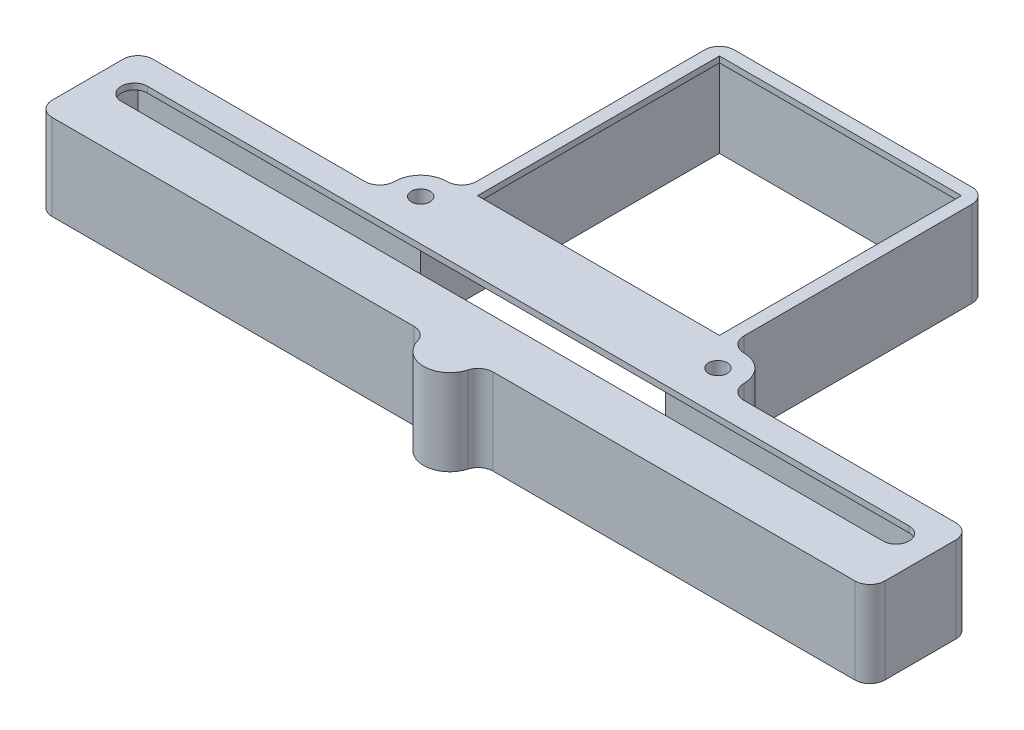
SolidWorks part; units mm, degrees
ref_plane "Front Plane" through (0, 0, 0) normal (0, 0, 1) x (1, 0, 0)
ref_plane "Top Plane" through (0, 0, 0) normal (0, 1, 0) x (1, 0, 0)
ref_plane "Right Plane" through (0, 0, 0) normal (1, 0, 0) x (0, 0, -1)
sketch "Sketch1" plane through (0, 0, 0) normal (0, 1, 0) x (1, 0, 0)
  line L0 (0, 36.3641) -> (0, -33.052) construction
  line L1 (-16.4, 25.25) -> (16.4, 25.25)
  line L2 (-16.4, 25.25) -> (-16.4, -25.25)
  line L3 (-16.4, -25.25) -> (16.4, -25.25)
  line L4 (16.4, 25.25) -> (16.4, -25.25)
  line L5 (-16.4, 25.25) -> (16.4, -25.25) construction
  line L6 (-16.4, -25.25) -> (16.4, 25.25) construction
  line L7 (-16.4, -25.25) -> (-16.4, -26.75) construction
  line L12 (-54.25, -14.75) -> (-55.75, -14.75) construction
  line L13 (-54.25, -14.75) -> (54.25, -14.75)
  line L14 (17.9, -26.75) -> (-17.9, -26.75)
  line L15 (17.9, -26.75) -> (17.9, 26.75)
  line L16 (17.9, 26.75) -> (-17.9, 26.75)
  line L17 (-17.9, -26.75) -> (-17.9, 26.75)
  line L18 (17.9, -26.75) -> (-17.9, 26.75) construction
  line L19 (17.9, 26.75) -> (-17.9, -26.75) construction
  line L20 (-16.4, 25.25) -> (-17.9, 25.25) construction
  line L21 (-16.4, 25.25) -> (-16.4, 26.75) construction
  line L22 (-54.25, -14.75) -> (-54.25, -25.25)
  line L23 (-54.25, -25.25) -> (54.25, -25.25)
  line L24 (54.25, -14.75) -> (54.25, -25.25)
  line L25 (-54.25, -14.75) -> (54.25, -25.25) construction
  line L26 (-54.25, -25.25) -> (54.25, -14.75) construction
  line L27 (-55.75, -13.25) -> (55.75, -13.25)
  line L28 (-55.75, -13.25) -> (-55.75, -26.75)
  line L29 (-55.75, -26.75) -> (55.75, -26.75)
  line L30 (55.75, -13.25) -> (55.75, -26.75)
  line L31 (-55.75, -13.25) -> (55.75, -26.75) construction
  line L32 (-55.75, -26.75) -> (55.75, -13.25) construction
  line L33 (-2, -27.25) -> (-3.5, -27.25) construction
  line L34 (-3.5, -27.25) -> (-3.5, -26.75)
  line L35 (3.5, -27.25) -> (3.5, -26.75)
  line L36 (-2, -27.25) -> (-2, -25.25)
  line L37 (2, -27.25) -> (2, -25.25)
  circle A0 centre (0, -27.25) radius 2
  circle A1 centre (0, -27.25) radius 3.5
  point P0 (0, 0)
  point P7 (0, -20)
  point P11 (0, -20)
  point P13 (0, 0)
  dimension "D6" = 4
  dimension "D1" = 32.8
  dimension "D2" = 50.5
  dimension "D3" = 1.5
  dimension "D4" = 108.5
  dimension "D5" = 10.5
extrude "Boss-Extrude1" add sketch "Sketch1" along normal blind 11.5 contours L17 L16 L15 L14 | L27 L30 L29 L28 | A1
sketch "Sketch2" plane through (0, 11.5, 0) normal (0, 1, 0) x (1, 0, 0)
  line L0 (0, 26.75) -> (0, -30.75) construction
  line L1 (17.9, 26.75) -> (-17.9, 26.75) construction
  line L3 (-16.2, 25.05) -> (-17.9, 25.05) construction
  line L4 (-16.2, -7.35) -> (16.2, -7.35)
  line L5 (-16.2, -7.35) -> (-16.2, 25.05)
  line L6 (-16.2, 25.05) -> (16.2, 25.05)
  line L7 (16.2, -7.35) -> (16.2, 25.05)
  line L8 (-16.2, -7.35) -> (16.2, 25.05) construction
  line L9 (-16.2, 25.05) -> (16.2, -7.35) construction
  line L10 (-17.9, -13.25) -> (-17.9, 26.75) construction
  line L11 (-16.2, 25.05) -> (-16.2, 26.75) construction
  arc A0 (-3.4641, -26.75) -> (3.4641, -26.75) centre (0, -27.25) ccw construction
  point P4 (0, 0)
  point P5 (0, 0)
  point P6 (0, 8.85)
  point P11 (0, -30.75)
  dimension "D1" = 32.4
extrude "Cut-Extrude1" cut sketch "Sketch2" against normal blind 8.7
sketch "Sketch3" plane through (0, 0, 0) normal (0, -1, 0) x (1, 0, 0)
  line L0 (-55.75, 20) -> (55.75, 20) construction
  line L1 (-55.75, 13.25) -> (-55.75, 26.75) construction
  line L2 (55.75, 13.25) -> (55.75, 26.75) construction
  line L3 (0, 30.75) -> (0, -26.75) construction
  line L4 (55.75, 26.75) -> (3.4641, 26.75) construction
  line L5 (17.9, -26.75) -> (-17.9, -26.75) construction
  line L6 (-54.25, 25.25) -> (-55.75, 25.25) construction
  line L7 (-54.25, 25.25) -> (54.25, 25.25)
  line L8 (-54.25, 25.25) -> (-54.25, 14.75)
  line L9 (-54.25, 14.75) -> (54.25, 14.75)
  line L10 (54.25, 25.25) -> (54.25, 14.75)
  line L11 (-54.25, 25.25) -> (54.25, 14.75) construction
  line L12 (-54.25, 14.75) -> (54.25, 25.25) construction
  line L13 (-54.25, 25.25) -> (-54.25, 26.75) construction
  line L14 (-2, 27.25) -> (-2, 25.25)
  line L15 (2, 27.25) -> (2, 25.25)
  arc A0 (3.4641, 26.75) -> (-3.4641, 26.75) centre (0, 27.25) ccw construction
  circle A1 centre (0, 27.25) radius 2
  point P12 (0, 20)
  dimension "D2" = 4
  dimension "D1" = 1.5
extrude "Cut-Extrude2" cut sketch "Sketch3" against normal offset from surface (10.7 mm away) 0.8 contours A1 | A1 L14 L7 | A1 L7 L15 | L10 L7 L8 L9 region at (0, 0, 20) region at (-1.5533, 0, 25.6967) region at (1.5533, 0, 25.6967) region at (0, 0, 27.25) up to face at (0, 11.5, -8.85)
sketch "Sketch4" plane through (0, 10.7, 0) normal (0, -1, 0) x (1, 0, 0)
  line L0 (-54.25, 18.5) -> (54.25, 18.5) construction
  line L1 (-54.25, 14.75) -> (-54.25, 25.25) construction
  line L2 (54.25, 25.25) -> (54.25, 14.75) construction
  line L3 (54.25, 14.75) -> (-54.25, 14.75) construction
  line L4 (51, 18.5) -> (-51, 18.5) construction
  line L5 (51, 16.75) -> (-51, 16.75)
  line L6 (51, 20.25) -> (-51, 20.25)
  arc A0 (51, 16.75) -> (51, 20.25) centre (51, 18.5) ccw
  arc A1 (-51, 20.25) -> (-51, 16.75) centre (-51, 18.5) ccw
  point P10 (0, 18.5)
  dimension "D1" = 3.75
  dimension "D2" = 3.5
  dimension "D3" = 102
extrude "Cut-Extrude3" cut sketch "Sketch4" against normal up to next
sketch "Sketch5" plane through (0, 0, 0) normal (0, -1, 0) x (1, 0, 0)
  line L0 (-17.9, -6.75) -> (17.9, -6.75) construction
  line L1 (-17.9, 13.25) -> (-17.9, -26.75) construction
  line L2 (17.9, 13.25) -> (17.9, -26.75) construction
  line L3 (-17.9, 13.25) -> (17.9, 13.25) construction
  line L4 (0, -26.75) -> (0, 13.25) construction
  line L5 (17.9, -26.75) -> (-17.9, -26.75) construction
  line L7 (-16.4, 14.75) -> (16.4, 14.75)
  line L8 (-16.4, 14.75) -> (-16.4, -25.25)
  line L9 (-16.4, -25.25) -> (16.4, -25.25)
  line L10 (16.4, 14.75) -> (16.4, -25.25)
  line L11 (-16.4, 14.75) -> (16.4, -25.25) construction
  line L12 (-16.4, -25.25) -> (16.4, 14.75) construction
  line L13 (54.25, 14.75) -> (-54.25, 14.75) construction
  line L14 (16.4, -25.25) -> (17.9, -25.25) construction
  line L15 (16.4, -25.25) -> (16.4, -26.75) construction
  point P14 (0, -5.25)
  dimension "D1" = 1.5
extrude "Cut-Extrude4" cut sketch "Sketch5" against normal up to surface (10.7 mm away) up to face at (0, 10.7, 18.5)
sketch "Sketch6" plane through (0, 10.7, 0) normal (0, -1, 0) x (1, 0, 0)
  line L0 (-16.4, -25.25) -> (-16.4, 14.75) construction
  line L1 (-16.4, 7.35) -> (16.4, 7.35)
  line L2 (-16.4, 7.35) -> (-16.4, 8.85)
  line L3 (-16.4, 8.85) -> (16.4, 8.85)
  line L4 (16.4, 7.35) -> (16.4, 8.85)
  line L5 (16.4, -25.25) -> (16.4, 14.75) construction
  line L7 (-16.2, 7.35) -> (16.2, 7.35) construction
  dimension "D1" = 1.5
extrude "Boss-Extrude2" add sketch "Sketch6" along normal offset from surface (7.7 mm away) 8.5 up to face at (0, 11.5, 18.5)
sketch "Sketch8" plane through (0, 11.5, 0) normal (0, 1, 0) x (1, 0, 0)
  line L0 (-55.75, -13.25) -> (-17.9, -13.25) construction
  line L2 (0, 31.5428) -> (0, -38.2394) construction
  line L3 (-19.9, -7.75) -> (-17.9, -7.75)
  line L4 (-17.9, -13.25) -> (-17.9, 26.75) construction
  line L5 (-23.4, -11.25) -> (-23.4, -13.25)
  line L6 (23.4, -11.25) -> (23.4, -13.25)
  line L7 (19.9, -7.75) -> (17.9, -7.75)
  line L8 (-23.4, -13.25) -> (-17.9, -13.25)
  line L9 (-17.9, -13.25) -> (-17.9, -7.75)
  line L10 (17.9, -13.25) -> (17.9, -7.75)
  line L11 (23.4, -13.25) -> (17.9, -13.25)
  circle A0 centre (-19.9, -11.25) radius 2
  circle A1 centre (19.9, -11.25) radius 2
  circle A2 centre (-19.9, -11.25) radius 3.5
  circle A3 centre (19.9, -11.25) radius 3.5
  circle A4 centre (-19.9, -11.25) radius 1.25
  circle A5 centre (19.9, -11.25) radius 1.25
  line M16 (-17.9, 26.75) -> (-17.9, -13.25)
  line M17 (-17.9, -13.25) -> (-55.75, -13.25)
  line M21 (55.75, -13.25) -> (17.9, -13.25)
  line M22 (17.9, -13.25) -> (17.9, 26.75)
  dimension "D1" = 4
  dimension "D3" = 1.5
  dimension "D2" = 2.5
extrude "Boss-Extrude5" add sketch "Sketch8" against normal up to surface (11.5 mm away) contours A2 L3 M16 | L9 A2 L8 A0 | A0 A4 | A0 L9 M17 | A2 L5 M17 | L11 A1 M22 | A1 A5 | A3 L10 A1 L11 | A3 L7 M22 | L6 A3 M21 region at (-18.8752, 11.5, 7.9848) region at (-18.3906, 11.5, 7.935) region at (-23.215, 11.5, 12.7594) region at (-18.5258, 11.5, 12.6242) region at (-18.3467, 11.5, 12.8033) region at (23.1652, 11.5, 12.2748) region at (23.215, 11.5, 12.7594) region at (18.3906, 11.5, 7.935) region at (18.3467, 11.5, 12.8033) region at (18.5258, 11.5, 12.6242) up to face at (0, 0, 13.8333)
fillet "Fillet1" radius 2 12 edges at (55.75, 5.75, 26.75) (55.75, 5.75, 13.25) (-55.75, 5.75, 26.75) (-55.75, 5.75, 13.25) (-17.9, 5.75, -26.75) (17.9, 5.75, -26.75) (-17.9, 5.75, 7.75) (-23.4, 5.75, 13.25) (23.4, 5.75, 13.25) (17.9, 5.75, 7.75) (-3.4641, 5.75, 26.75) (3.4641, 5.75, 26.75)
